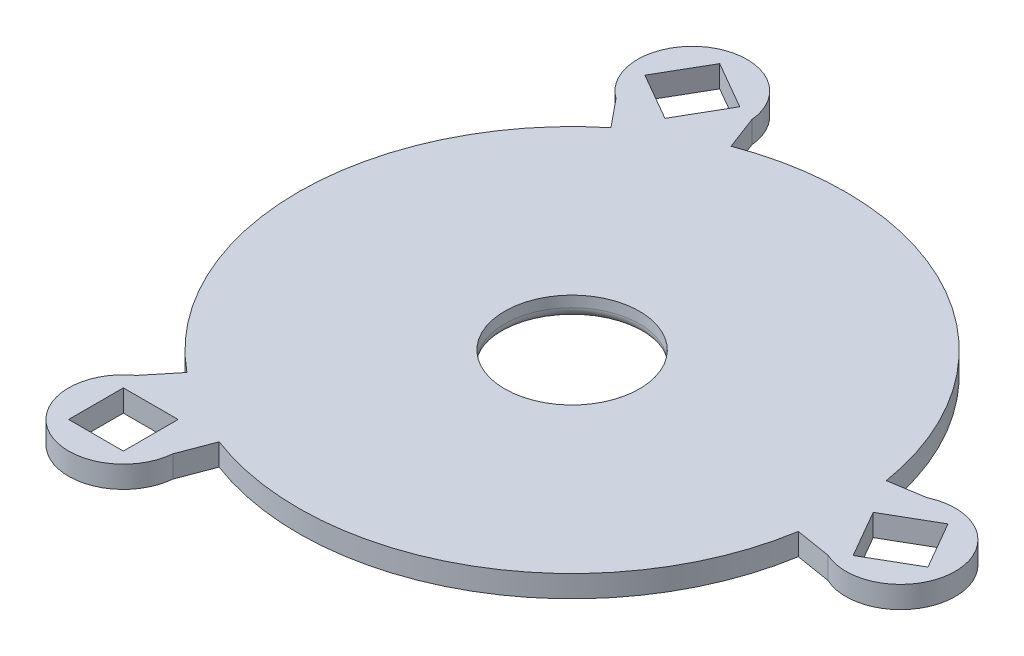
SolidWorks part; units mm, degrees
ref_plane "Front Plane" through (0, 0, 0) normal (0, 0, 1) x (1, 0, 0)
ref_plane "Top Plane" through (0, 0, 0) normal (0, 1, 0) x (1, 0, 0)
ref_plane "Right Plane" through (0, 0, 0) normal (1, 0, 0) x (0, 0, -1)
sketch "Sketch1" plane through (0, 0, 0) normal (0, 1, 0) x (1, 0, 0)
  line L0 (0, 0) -> (-15, -25.9808) construction
  line L4 (-17.5, -23.4808) -> (-12.5, -23.4808)
  line L5 (-17.5, -23.4808) -> (-17.5, -28.4808)
  line L6 (-17.5, -28.4808) -> (-12.5, -28.4808)
  line L7 (-12.5, -23.4808) -> (-12.5, -28.4808)
  line L8 (0, 0) -> (-17.8866, -21.8982)
  line L15 (0, 0) -> (-10.0211, -26.4394)
  line L16 (-11.5849, 26.8958) -> (-14.0849, 22.5657)
  line L17 (-11.5849, 26.8958) -> (-15.9151, 29.3958)
  line L18 (-15.9151, 29.3958) -> (-18.4151, 25.0657)
  line L19 (-14.0849, 22.5657) -> (-18.4151, 25.0657)
  line L20 (0, 0) -> (-10.0211, 26.4394)
  line L21 (0, 0) -> (-15, 25.9808) construction
  line L22 (0, 0) -> (-17.8866, 21.8982)
  line L23 (29.0849, -3.4151) -> (26.5849, 0.9151)
  line L24 (29.0849, -3.4151) -> (33.4151, -0.9151)
  line L25 (33.4151, -0.9151) -> (30.9151, 3.4151)
  line L26 (26.5849, 0.9151) -> (30.9151, 3.4151)
  line L27 (0, 0) -> (27.9077, -4.5412)
  line L28 (0, 0) -> (30, 0) construction
  line L29 (0, 0) -> (27.9077, 4.5412)
  line L30 (0, 0) -> (0, -25) construction
  circle A0 centre (0, 0) radius 25
  arc A1 (-17.8866, -21.8982) -> (-10.0211, -26.4394) centre (-15, -25.9808) ccw
  arc A2 (-10.0211, 26.4394) -> (-17.8866, 21.8982) centre (-15, 25.9808) ccw
  arc A3 (27.9077, -4.5412) -> (27.9077, 4.5412) centre (30, 0) ccw
  point P8 (-15, -28.4808)
  point P9 (-17.5, -25.9808)
  point P29 (0, 0)
  dimension "D1" = 50
  dimension "D5" = 5
  dimension "D2" = 30
  dimension "D3" = 5
  dimension "D4" = 28.2748
  dimension "D6" = 3
  dimension "D7" = 120
  dimension "D8" = 120
  dimension "D9" = 120
  dimension "D10" = 30
extrude "Boss-Extrude1" add sketch "Sketch1" along normal blind 2 contours L8 A1 L15 A0 L4 L7 L6 L5 | L27 A3 L29 A0 L23 L26 L25 L24 | L20 A2 L22 A0 L16 L19 L18 L17 | A0 region at (-12.5805, 0, 21.79) region at (-12.5805, 0, -21.79) region at (25.062, 0, 2.0257)
ref_plane "top_face" through (0, 0, 0) normal (0, -1, 0) x (-1, 0, 0)
sketch "Sketch2" plane through (0, 0, 0) normal (0, -1, 0) x (-1, 0, 0)
  circle A0 centre (0, 0) radius 6.15
  dimension "D1" = 12.3
extrude "Cut-Extrude1" cut sketch "Sketch2" against normal up to next
ref_axis "Axis1" through (0, 2, 0) along (0, -1, 0)
fillet "Fillet1" radius 1 1 edges at (0, 0, -6.15)
